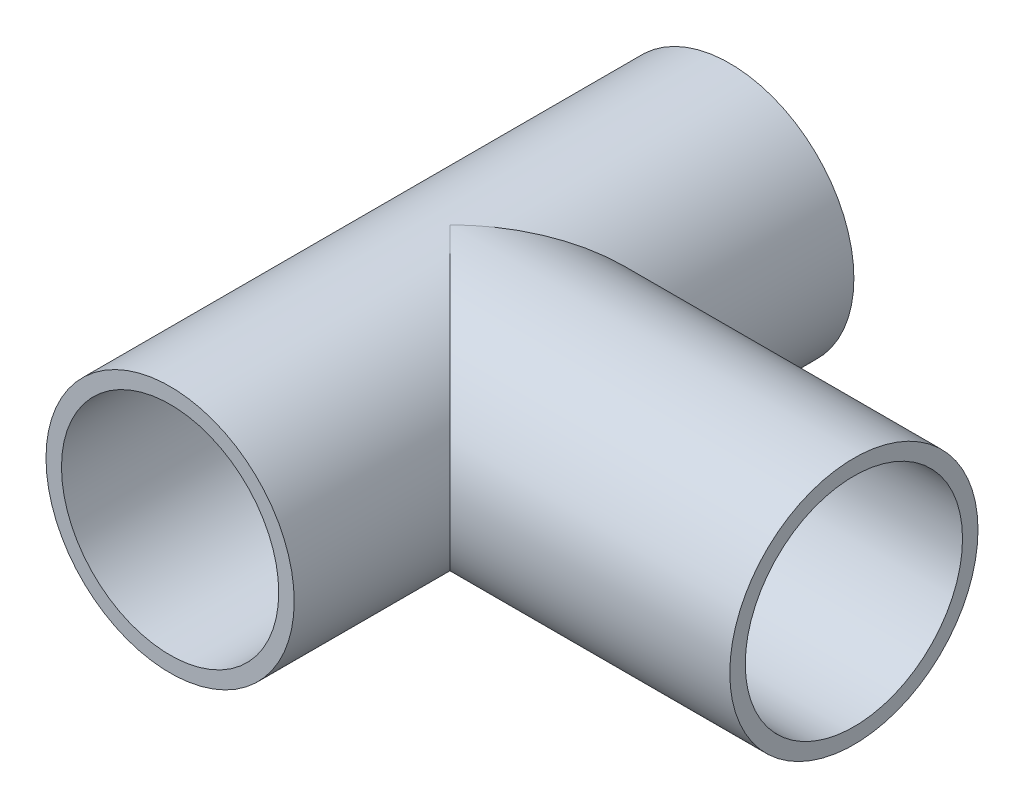
SolidWorks part; units mm, degrees
material "PE High Density"
ref_plane "Front Plane" through (0, 0, 0) normal (0, 0, 1) x (1, 0, 0)
ref_plane "Top Plane" through (0, 0, 0) normal (0, 1, 0) x (1, 0, 0)
ref_plane "Right Plane" through (0, 0, 0) normal (1, 0, 0) x (0, 0, -1)
sketch "Through Section" plane through (0, 0, 0) normal (0, 0, 1) x (1, 0, 0)
  circle A0 centre (0, 0) radius 161.925
  circle A1 centre (0, 0) radius 141.732
  dimension "D1" = 283.464
  dimension "D2" = 323.85
extrude "Through Section Extrude" add sketch "Through Section" along normal blind 730.25
ref_plane "E Plane" through (527.05, 0, 0) normal (1, 0, 0) x (0, 0, -1)
sketch "Orthogonal Section OD" plane through (527.05, 0, 0) normal (1, 0, 0) x (0, 0, -1)
  line L1 (-730.25, -161.925) -> (0, -161.925) construction
  circle A0 centre (-365.125, 0) radius 161.925
  dimension "D3" = 323.85
  dimension "D1" = 365.125
  dimension "D2" = 161.925
extrude "Orthogonal Section OD Extrude" add sketch "Orthogonal Section OD" against normal up to surface (365.125 mm away) up to face at (161.925, 0, 730.25)
sketch "Orthogonal Section ID" plane through (527.05, 0, 0) normal (1, 0, 0) x (0, 0, -1)
  circle A0 centre (-365.125, 0) radius 141.732
  circle A1 centre (-365.125, 0) radius 161.925 construction
  dimension "D1" = 283.464
extrude "Orthogonal Section ID Cut" cut sketch "Orthogonal Section ID" against normal up to surface (527.05 mm away) up to plane "Right Plane"
equation "\"ID\"= 11.160in'EPG"
equation "\"OD\"= 12.75'EPG"
equation "\"A\"= 8in'EPG"
equation "\"C\"= 28.75in'EPG"
equation "\"E\"= 8in'EPG"
equation "\"D1@Through Section\" = \"ID\""
equation "\"D2@Through Section\" = \"OD\""
equation "\"D1@Through Section Extrude\" = \"C\""
equation "\"D1@Orthogonal Section OD\" = \"C\" / 2"
equation "\"D2@Orthogonal Section OD\" = \"OD\" / 2"
equation "\"D3@Orthogonal Section OD\" = \"OD\""
equation "\"D1@Orthogonal Section ID\" = \"ID\""
